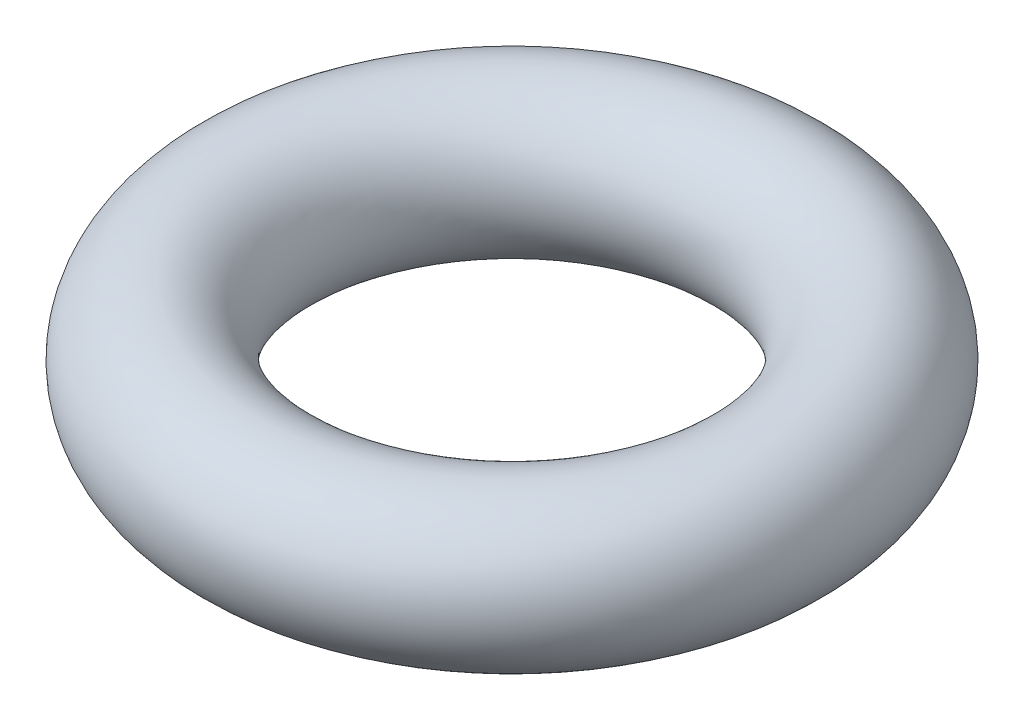
SolidWorks part; units mm, degrees
ref_plane "Front Plane" through (0, 0, 0) normal (0, 0, 1) x (1, 0, 0)
ref_plane "Top Plane" through (0, 0, 0) normal (0, 1, 0) x (1, 0, 0)
ref_plane "Right Plane" through (0, 0, 0) normal (1, 0, 0) x (0, 0, -1)
sketch "Sketch1" plane through (0, 0, 0) normal (0, 1, 0) x (1, 0, 0)
  circle A1 centre (0, 0) radius 3.937
  dimension "B" = 7.874
sketch "Sketch2" plane through (0, 0, 0) normal (0, 0, 1) x (1, 0, 0)
  circle A0 centre (-5.588, 0) radius 1.651
  point P4 (-3.937, 0)
  dimension "A" = 3.302
sweep "Sweep1" add profiles "Sketch2" path "Sketch1"
ref_axis "Axis1" through (0, 5.2562, 0) along (0, -1, 0)
